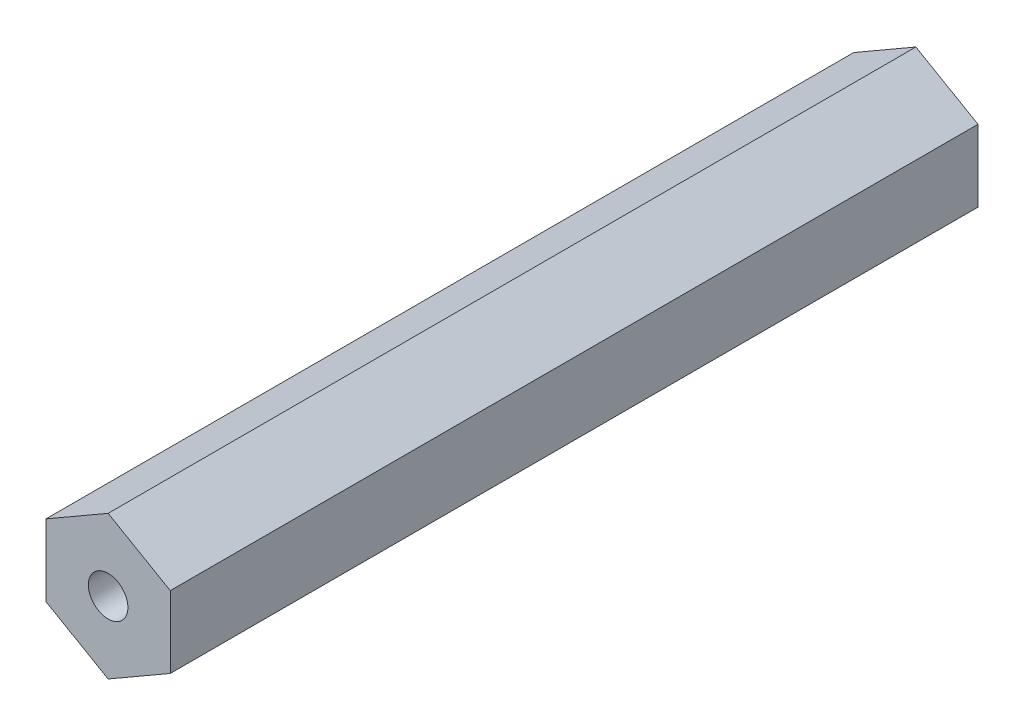
SolidWorks part; units mm, degrees
other "Markup1"
sketch "Sketch3" plane through (6.35, 7.3323, -19.05) normal (0.3384, 0.0641, -0.9388) x (-0.9259, -0.1556, -0.3443)
material "7075-T6 (SN)"
ref_plane "Front Plane" through (0, 0, 0) normal (0, 0, 1) x (1, 0, 0)
ref_plane "Top Plane" through (0, 0, 0) normal (0, 1, 0) x (1, 0, 0)
ref_plane "Right Plane" through (0, 0, 0) normal (1, 0, 0) x (0, 0, -1)
sketch "Sketch1" plane through (0, 0, 0) normal (0, 0, 1) x (1, 0, 0)
  line L1 (0, 7.3323) -> (-6.35, 3.6662)
  line L2 (-6.35, 3.6662) -> (-6.35, -3.6662)
  line L3 (-6.35, -3.6662) -> (0, -7.3323)
  line L4 (0, -7.3323) -> (6.35, -3.6662)
  line L5 (6.35, -3.6662) -> (6.35, 3.6662)
  line L6 (6.35, 3.6662) -> (0, 7.3323)
  circle A0 centre (0, 0) radius 6.35 construction
  dimension "D1" = 12.7
extrude "Boss-Extrude1" add sketch "Sketch1" along normal mid plane 82.55
sketch "Sketch2" plane through (0, 0, -41.275) normal (0, 0, -1) x (-1, 0, 0)
  circle A0 centre (0, 0) radius 2.0193
  dimension "D1" = 4.0386
sketch "Sketch4" plane through (0, 0, -41.275) normal (0, 0, -1) x (-1, 0, 0)
  point P0 (0, 0)
hole_wizard "#10-32 Tapped Hole1" positions "Sketch4" profile "Sketch5" tap size "#10-32" standard "ANSI Inch"
sketch "Sketch5" plane through (0, 0, -41.275) normal (1, 0, 0) x (0, 1, 0)
  line L0 (0, 0) -> (0, 13.1513)
  line L1 (0, 13.1513) -> (2.0193, 11.938)
  line L2 (2.0193, 11.938) -> (2.0193, 0)
  line L5 (2.0193, 0) -> (0, 0)
  line L10 (0, 13.1513) -> (-2.0193, 11.938) construction
  line L11 (0, -6.35) -> (0, 107.95) construction
  dimension "Tap Drill Dia." = 4.0386
  dimension "Tap Drill Depth" = 11.938
  dimension "Drill Angle" = 118
cosmetic thread "Hole Thread1" parameters "D1"=9.652, "D2"=4.826
mirror "Mirror1" about plane through (0, 0, 0) normal (0, 0, 1) of "#10-32 Tapped Hole1"
cosmetic thread "Hole Thread2" parameters "D1"=9.652, "D2"=4.826
